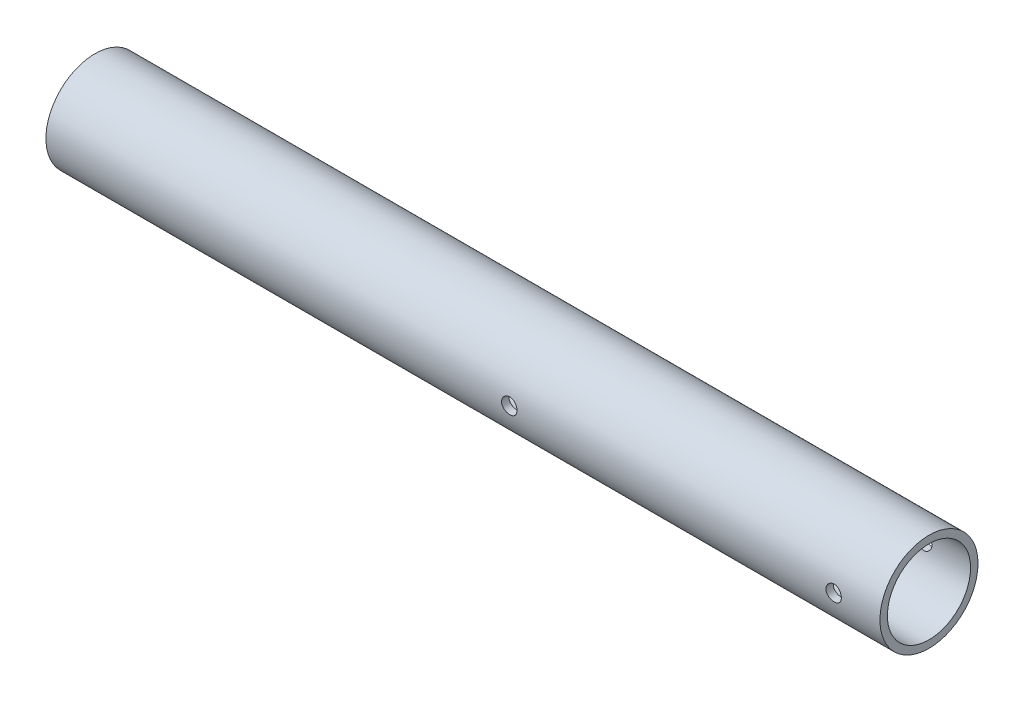
SolidWorks part; units mm, degrees
ref_plane "Front Plane" through (0, 0, 0) normal (0, 0, 1) x (1, 0, 0)
ref_plane "Top Plane" through (0, 0, 0) normal (0, 1, 0) x (1, 0, 0)
ref_plane "Right Plane" through (0, 0, 0) normal (1, 0, 0) x (0, 0, -1)
sketch "Sketch1" plane through (0, 0, 0) normal (1, 0, 0) x (0, 0, -1)
  circle A0 centre (0, 0) radius 13.462
  circle A1 centre (0, 0) radius 15.875
  point P5 (1.4273, -2.0793)
  point P6 (0, 0)
  point P7 (0, -0.0938)
  dimension "D1" = 31.75
  dimension "D2" = 2.413
extrude "Boss-Extrude1" add sketch "Sketch1" along normal blind 120 and the other way blind 150
sketch "Sketch2" plane through (0, 0, 0) normal (0, 0, 1) x (1, 0, 0)
  line L0 (0, 0) -> (120, 0) construction
  line L1 (120, -15.875) -> (120, 15.875) construction
  circle A0 centre (0, 0) radius 2.5
  circle A1 centre (105, 0) radius 2.5
  dimension "D1" = 5
  dimension "D2" = 105
extrude "Cut-Extrude1" cut sketch "Sketch2" against normal blind 150 and the other way blind 150
sketch "Sketch3" plane through (0, 0, 0) normal (0, 0, 1) x (1, 0, 0)
  line L0 (0, 0) -> (120, 0) construction
  line L1 (120, -15.875) -> (120, 15.875) construction
  line L2 (25, 0) -> (100, 0) construction
  line L3 (25, 2.5) -> (100, 2.5)
  line L4 (25, -2.5) -> (100, -2.5)
  arc A0 (25, 2.5) -> (25, -2.5) centre (25, 0) ccw
  arc A1 (100, -2.5) -> (100, 2.5) centre (100, 0) ccw
  point P7 (62.5, 0)
  dimension "D1" = 25
  dimension "D2" = 5
  dimension "D3" = 75
extrude "Cut-Extrude2" cut sketch "Sketch3" against normal blind 150 and the other way blind 150 rebuild error yes
